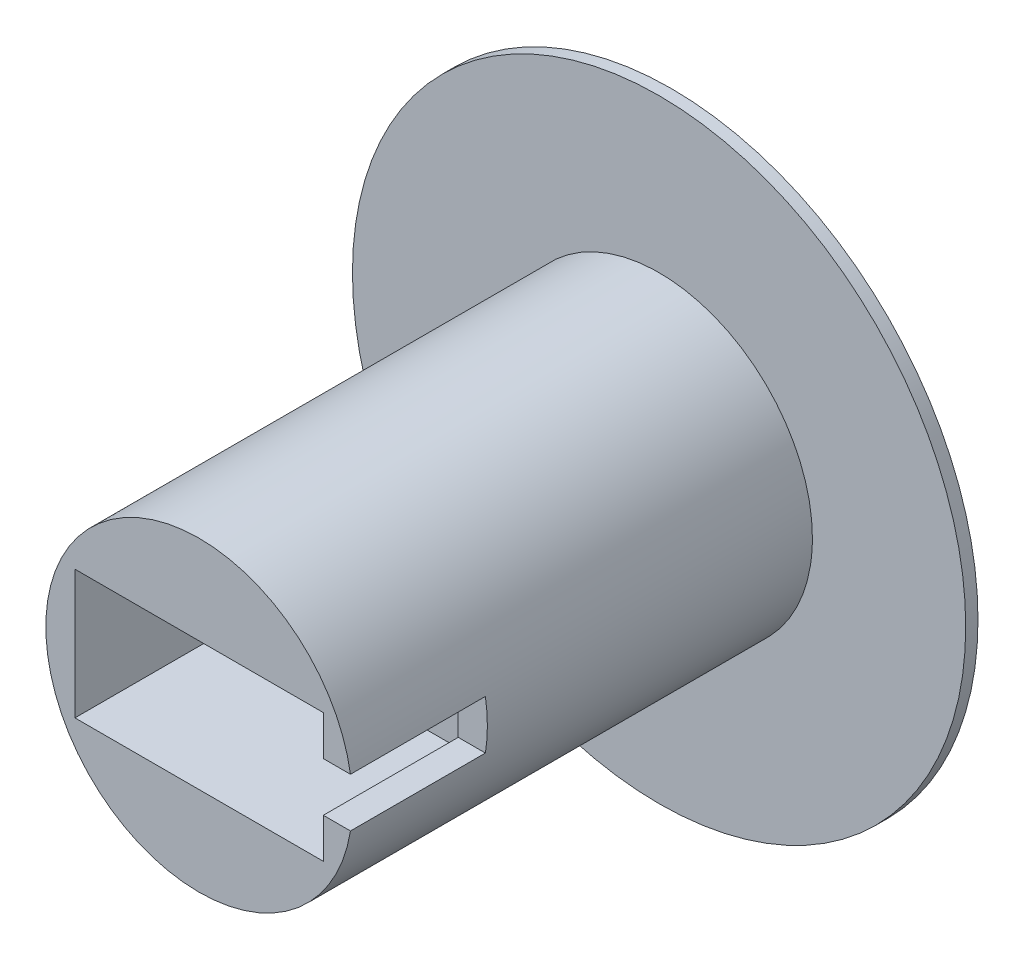
SolidWorks part; units mm, degrees
ref_plane "前视基准面" through (0, 0, 0) normal (0, 0, 1) x (1, 0, 0)
ref_plane "上视基准面" through (0, 0, 0) normal (0, 1, 0) x (1, 0, 0)
ref_plane "右视基准面" through (0, 0, 0) normal (1, 0, 0) x (0, 0, -1)
other "Configuration Table"
sketch "Sketch1" plane through (0, 0, 0) normal (0, 0, 1) x (1, 0, 0)
  line L1 (-20.25, 10.5) -> (20.25, 10.5)
  line L2 (-20.25, 10.5) -> (-20.25, -10.5)
  line L3 (-20.25, -10.5) -> (20.25, -10.5)
  line L4 (20.25, 10.5) -> (20.25, -10.5)
  line L5 (0, -10.5) -> (0, 10.5) construction
  line L6 (-20.25, 0) -> (20.25, 0) construction
  line L7 (15.5, 4) -> (25, 4)
  line L8 (15.5, 4) -> (15.5, -4)
  line L9 (15.5, -4) -> (25, -4)
  line L10 (25, 4) -> (25, -4)
  line L11 (20.25, -4) -> (20.25, 4) construction
  line L12 (15.5, 0) -> (25, 0) construction
  circle A0 centre (0, 0) radius 50
  circle A1 centre (0, 0) radius 25
  dimension "D1" = 21
  dimension "D2" = 40.5
  dimension "D3" = 8
  dimension "D4" = 9.5
extrude "Boss-Extrude1" add sketch "Sketch1" along normal blind 2 contours A0 A1 L7 L10 L9 | A1 L9 L10 | A1 L10 L7 region at (24.9035, 3.0013, 0) region at (24.9035, -3.0013, 0) region at (-48.5858, 0, 0)
extrude "Boss-Extrude2" add sketch "Sketch1<3>" along normal blind 50 separate body contours L9 L8 L7 L4 L1 L2 L3 | L8 L9 L4 L7 region at (-0.836, 0, 0) region at (17.875, 0, 0)
sketch "Sketch1<3>" plane through (0, 0, 0) normal (0, 0, 1) x (1, 0, 0) same geometry as "Sketch1"
extrude "Boss-Extrude3" add sketch "Sketch1<4>" along normal blind 77 contours L7 A1 L9 L4 L3 L2 L1 region at (-20.9548, 0, 0)
sketch "Sketch1<4>" plane through (0, 0, 0) normal (0, 0, 1) x (1, 0, 0) same geometry as "Sketch1"
extrude "Boss-Extrude7" add sketch "Sketch1<7>" along normal blind 55 contours A1 L7 L4 L9 region at (22.5725, 0, 0)
sketch "Sketch1<7>" plane through (0, 0, 0) normal (0, 0, 1) x (1, 0, 0) same geometry as "Sketch1"
